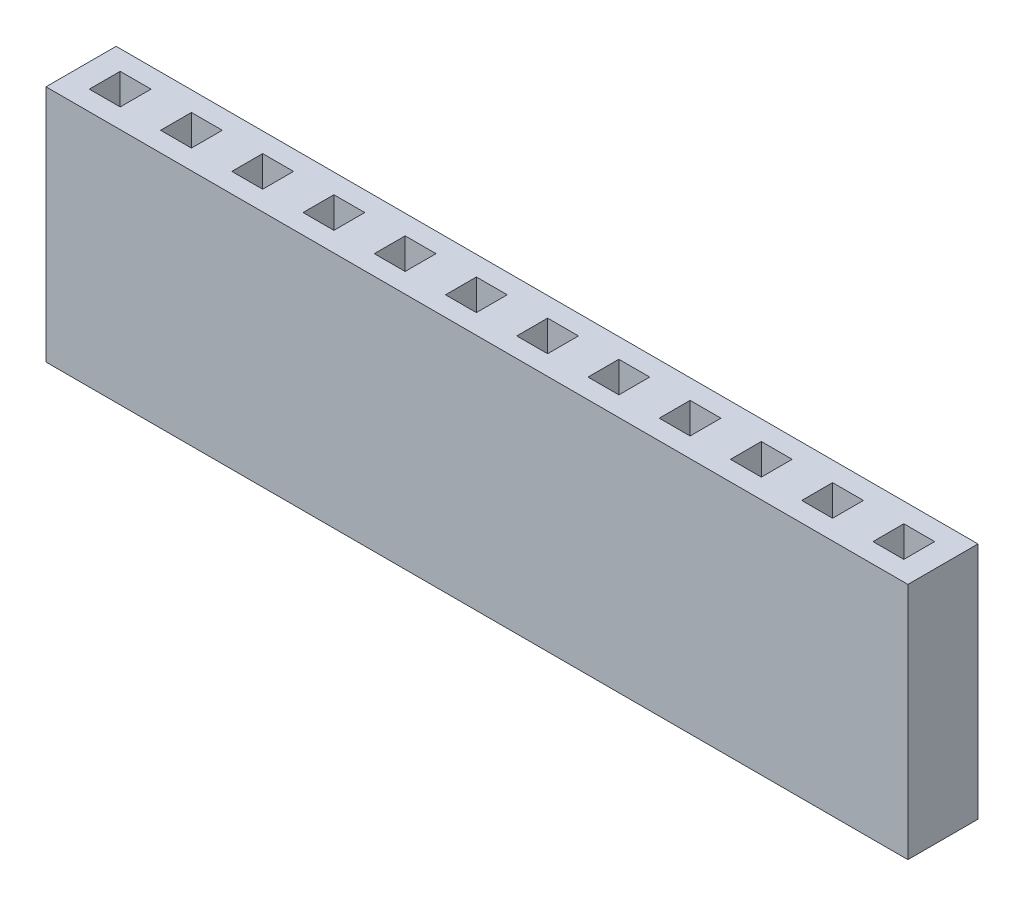
SolidWorks part; units mm, degrees
ref_plane "Front Plane" through (0, 0, 0) normal (0, 0, 1) x (1, 0, 0)
ref_plane "Top Plane" through (0, 0, 0) normal (0, 1, 0) x (1, 0, 0)
ref_plane "Right Plane" through (0, 0, 0) normal (1, 0, 0) x (0, 0, -1)
sketch "Sketch1" plane through (0, 0, 0) normal (0, 0, 1) x (1, 0, 0)
  line L1 (0, 0) -> (30.73, 0)
  line L2 (0, 0) -> (0, 8.5)
  line L3 (0, 8.5) -> (30.73, 8.5)
  line L4 (30.73, 0) -> (30.73, 8.5)
  dimension "D1" = 8.5
  dimension "D2" = 30.73
extrude "Boss-Extrude1" add sketch "Sketch1" along normal mid plane 2.5
sketch "Sketch2" plane through (0, 0, 0) normal (0, -1, 0) x (1, 0, 0)
  line L0 (0, 0) -> (30.73, 0) construction
  line L1 (30.73, 1.25) -> (30.73, -1.25) construction
  line L2 (3.385, -0.55) -> (4.485, -0.55)
  line L3 (0.845, -0.55) -> (1.945, -0.55)
  line L4 (0.845, -0.55) -> (0.845, 0.55)
  line L5 (0.845, 0.55) -> (1.945, 0.55)
  line L6 (1.945, -0.55) -> (1.945, 0.55)
  line L7 (0.845, -0.55) -> (1.945, 0.55) construction
  line L8 (0.845, 0.55) -> (1.945, -0.55) construction
  line L9 (3.385, -0.55) -> (3.385, 0.55)
  line L10 (3.385, 0.55) -> (4.485, 0.55)
  line L11 (4.485, -0.55) -> (4.485, 0.55)
  line L12 (3.385, -0.55) -> (4.485, 0.55) construction
  line L13 (3.385, 0.55) -> (4.485, -0.55) construction
  line L14 (5.925, -0.55) -> (7.025, -0.55)
  line L15 (5.925, -0.55) -> (5.925, 0.55)
  line L16 (5.925, 0.55) -> (7.025, 0.55)
  line L17 (7.025, -0.55) -> (7.025, 0.55)
  line L18 (5.925, -0.55) -> (7.025, 0.55) construction
  line L19 (5.925, 0.55) -> (7.025, -0.55) construction
  line L20 (8.465, -0.55) -> (9.565, -0.55)
  line L21 (8.465, -0.55) -> (8.465, 0.55)
  line L22 (8.465, 0.55) -> (9.565, 0.55)
  line L23 (9.565, -0.55) -> (9.565, 0.55)
  line L24 (8.465, -0.55) -> (9.565, 0.55) construction
  line L25 (8.465, 0.55) -> (9.565, -0.55) construction
  line L26 (11.005, -0.55) -> (12.105, -0.55)
  line L27 (11.005, -0.55) -> (11.005, 0.55)
  line L28 (11.005, 0.55) -> (12.105, 0.55)
  line L29 (12.105, -0.55) -> (12.105, 0.55)
  line L30 (11.005, -0.55) -> (12.105, 0.55) construction
  line L31 (11.005, 0.55) -> (12.105, -0.55) construction
  line L32 (13.545, -0.55) -> (14.645, -0.55)
  line L33 (13.545, -0.55) -> (13.545, 0.55)
  line L34 (13.545, 0.55) -> (14.645, 0.55)
  line L35 (14.645, -0.55) -> (14.645, 0.55)
  line L36 (13.545, -0.55) -> (14.645, 0.55) construction
  line L37 (13.545, 0.55) -> (14.645, -0.55) construction
  line L38 (16.085, -0.55) -> (17.185, -0.55)
  line L39 (16.085, -0.55) -> (16.085, 0.55)
  line L40 (16.085, 0.55) -> (17.185, 0.55)
  line L41 (17.185, -0.55) -> (17.185, 0.55)
  line L42 (16.085, -0.55) -> (17.185, 0.55) construction
  line L43 (16.085, 0.55) -> (17.185, -0.55) construction
  line L44 (18.625, -0.55) -> (19.725, -0.55)
  line L45 (18.625, -0.55) -> (18.625, 0.55)
  line L46 (18.625, 0.55) -> (19.725, 0.55)
  line L47 (19.725, -0.55) -> (19.725, 0.55)
  line L48 (18.625, -0.55) -> (19.725, 0.55) construction
  line L49 (18.625, 0.55) -> (19.725, -0.55) construction
  line L50 (21.165, -0.55) -> (22.265, -0.55)
  line L51 (21.165, -0.55) -> (21.165, 0.55)
  line L52 (21.165, 0.55) -> (22.265, 0.55)
  line L53 (22.265, -0.55) -> (22.265, 0.55)
  line L54 (21.165, -0.55) -> (22.265, 0.55) construction
  line L55 (21.165, 0.55) -> (22.265, -0.55) construction
  line L56 (23.705, -0.55) -> (24.805, -0.55)
  line L57 (23.705, -0.55) -> (23.705, 0.55)
  line L58 (23.705, 0.55) -> (24.805, 0.55)
  line L59 (24.805, -0.55) -> (24.805, 0.55)
  line L60 (23.705, -0.55) -> (24.805, 0.55) construction
  line L61 (23.705, 0.55) -> (24.805, -0.55) construction
  line L62 (26.245, -0.55) -> (27.345, -0.55)
  line L63 (26.245, -0.55) -> (26.245, 0.55)
  line L64 (26.245, 0.55) -> (27.345, 0.55)
  line L65 (27.345, -0.55) -> (27.345, 0.55)
  line L66 (26.245, -0.55) -> (27.345, 0.55) construction
  line L67 (26.245, 0.55) -> (27.345, -0.55) construction
  line L68 (28.785, -0.55) -> (29.885, -0.55)
  line L69 (28.785, -0.55) -> (28.785, 0.55)
  line L70 (28.785, 0.55) -> (29.885, 0.55)
  line L71 (29.885, -0.55) -> (29.885, 0.55)
  line L72 (28.785, -0.55) -> (29.885, 0.55) construction
  line L73 (28.785, 0.55) -> (29.885, -0.55) construction
  line L98 (31.325, -0.55) -> (32.425, -0.55) [skipped]
  line L99 (31.325, -0.55) -> (31.325, 0.55) [skipped]
  line L100 (31.325, 0.55) -> (32.425, 0.55) [skipped]
  line L101 (32.425, -0.55) -> (32.425, 0.55) [skipped]
  line L102 (33.865, -0.55) -> (34.965, -0.55) [skipped]
  line L103 (33.865, -0.55) -> (33.865, 0.55) [skipped]
  line L104 (33.865, 0.55) -> (34.965, 0.55) [skipped]
  line L105 (34.965, -0.55) -> (34.965, 0.55) [skipped]
  line L106 (36.405, -0.55) -> (37.505, -0.55) [skipped]
  line L107 (36.405, -0.55) -> (36.405, 0.55) [skipped]
  line L108 (36.405, 0.55) -> (37.505, 0.55) [skipped]
  line L109 (37.505, -0.55) -> (37.505, 0.55) [skipped]
  line L110 (38.945, -0.55) -> (40.045, -0.55) [skipped]
  line L111 (38.945, -0.55) -> (38.945, 0.55) [skipped]
  line L112 (38.945, 0.55) -> (40.045, 0.55) [skipped]
  line L113 (40.045, -0.55) -> (40.045, 0.55) [skipped]
  line L114 (31.325, -0.55) -> (32.425, 0.55) construction
  line L115 (31.325, 0.55) -> (32.425, -0.55) construction
  line L116 (33.865, -0.55) -> (34.965, 0.55) construction
  line L117 (33.865, 0.55) -> (34.965, -0.55) construction
  line L118 (36.405, -0.55) -> (37.505, 0.55) construction
  line L119 (36.405, 0.55) -> (37.505, -0.55) construction
  line L120 (38.945, -0.55) -> (40.045, 0.55) construction
  line L121 (38.945, 0.55) -> (40.045, -0.55) construction
  point P5 (1.395, 0)
  point P10 (36.955, 0)
  point P11 (34.415, 0)
  point P12 (3.935, 0)
  point P17 (6.475, 0)
  point P22 (9.015, 0)
  point P27 (11.555, 0)
  point P32 (14.095, 0)
  point P37 (16.635, 0)
  point P42 (19.175, 0)
  point P47 (21.715, 0)
  point P52 (24.255, 0)
  point P57 (26.795, 0)
  point P62 (29.335, 0)
  point P67 (39.495, 0)
  point P68 (31.875, 0)
  dimension "D1" = 1.1
  dimension "D3" = 1.395
  dimension "D2" = 16
extrude "Cut-Extrude1" cut sketch "Sketch2" against normal through all
ref_axis "Axis1" through (1.395, 0, 0) along (0, -1, 0)
ref_axis "Axis2" through (29.335, 0, 0) along (0, -1, 0)
